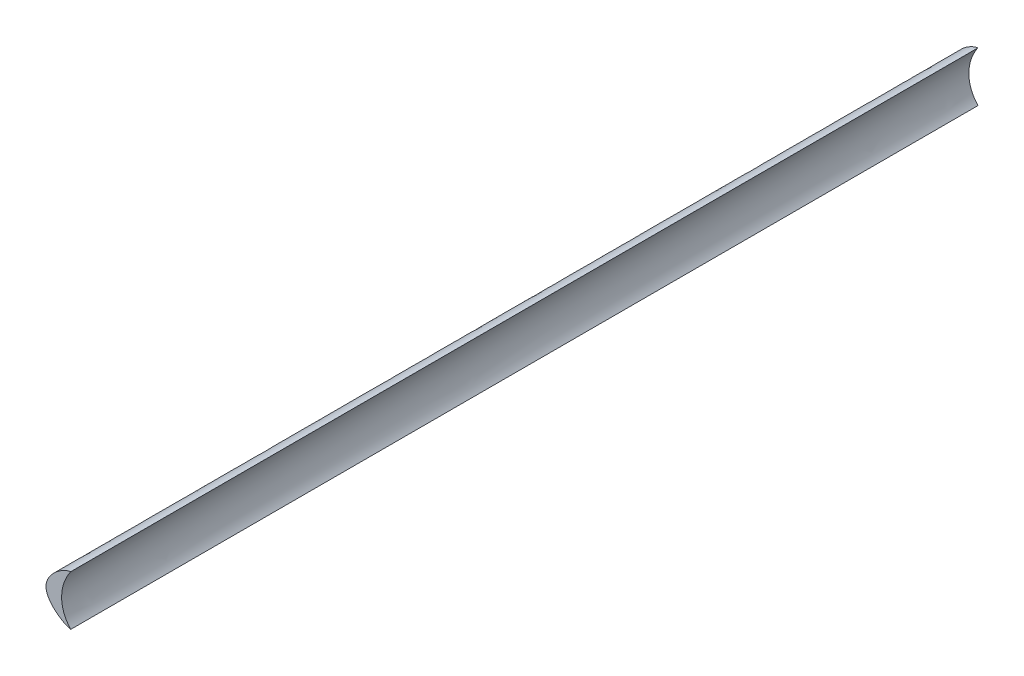
SolidWorks part; units mm, degrees
ref_plane "Front Plane" through (0, 0, 0) normal (0, 0, 1) x (1, 0, 0)
ref_plane "Top Plane" through (0, 0, 0) normal (0, 1, 0) x (1, 0, 0)
ref_plane "Right Plane" through (0, 0, 0) normal (1, 0, 0) x (0, 0, -1)
sketch "Sketch2" plane through (0, 0, 0) normal (0, 0, 1) x (1, 0, 0)
  spline S0 degree 3 poles (1.2338, 18.7945) (-6.8806, 7.6316) (-9.3632, -8.5346) (1.2338, -19.7752) knots 0 0 0 0 1 1 1 1
  spline S1 degree 3 poles (1.2338, 18.7945) (-6.3802, 17.5523) (-29.9338, -1.2032) (-5.3341, -18.6233) (1.2338, -19.7752) knots 0 0 0 0 0.514535 1 1 1 1
extrude "Boss-Extrude1" add sketch "Sketch2" along normal blind 350 and the other way blind 350
